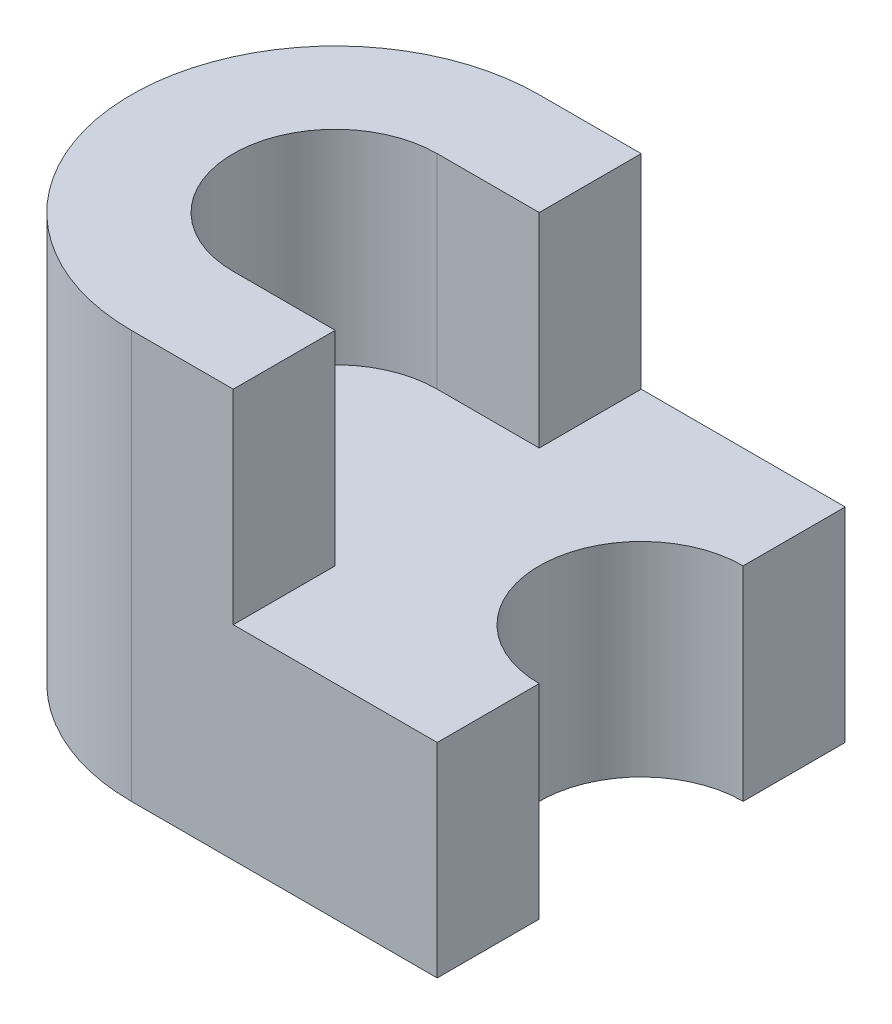
SolidWorks part; units mm, degrees
ref_plane "前基準面" through (0, 0, 0) normal (0, 0, 1) x (1, 0, 0)
ref_plane "上基準面" through (0, 0, 0) normal (0, 1, 0) x (1, 0, 0)
ref_plane "右基準面" through (0, 0, 0) normal (1, 0, 0) x (0, 0, -1)
sketch "草圖1" plane through (0, 0, 0) normal (0, 1, 0) x (1, 0, 0)
  line L0 (0, 0) -> (15, 0) construction
  line L1 (15, 0) -> (15, -3.7562) construction
  line L2 (0, 0) -> (0, 11.426) construction
  line L3 (5, 10) -> (5, 5)
  line L4 (0, 10) -> (15, 10)
  line L5 (15, 10) -> (15, 5)
  line L6 (15, -5) -> (15, -10)
  line L7 (15, -10) -> (0, -10)
  line L8 (0, 5) -> (5, 5)
  line L9 (0, -5) -> (5, -5)
  line L10 (5, -10) -> (5, -5)
  arc A0 (0, 10) -> (0, -10) centre (0, 0) ccw
  arc A1 (0, 5) -> (0, -5) centre (0, 0) ccw
  arc A2 (15, 5) -> (15, -5) centre (15, 0) ccw
  dimension "D1" = 15
  dimension "D2" = 10
  dimension "D3" = 20
  dimension "D4" = 10
  dimension "D5" = 5
extrude "填料-伸長1" add sketch "草圖1" along normal blind 10 contours A2 L5 L4 L3 L8 A1 L9 L10 L7 L6 | A1 L8 L3 L4 A0 L7 L10 L9 region at (6.1438, 0, 0) region at (4.75, 0, -7.5)
extrude "填料-伸長2" add sketch "草圖1<3>" along normal blind 20 contours A1 L8 L3 L4 A0 L7 L10 L9 region at (4.75, 0, -7.5)
sketch "草圖1<3>" plane through (0, 0, 0) normal (0, 1, 0) x (1, 0, 0) same geometry as "草圖1"
scale "縮放比例1" scale about centroid uniform scaling yes scale factor 0.2
